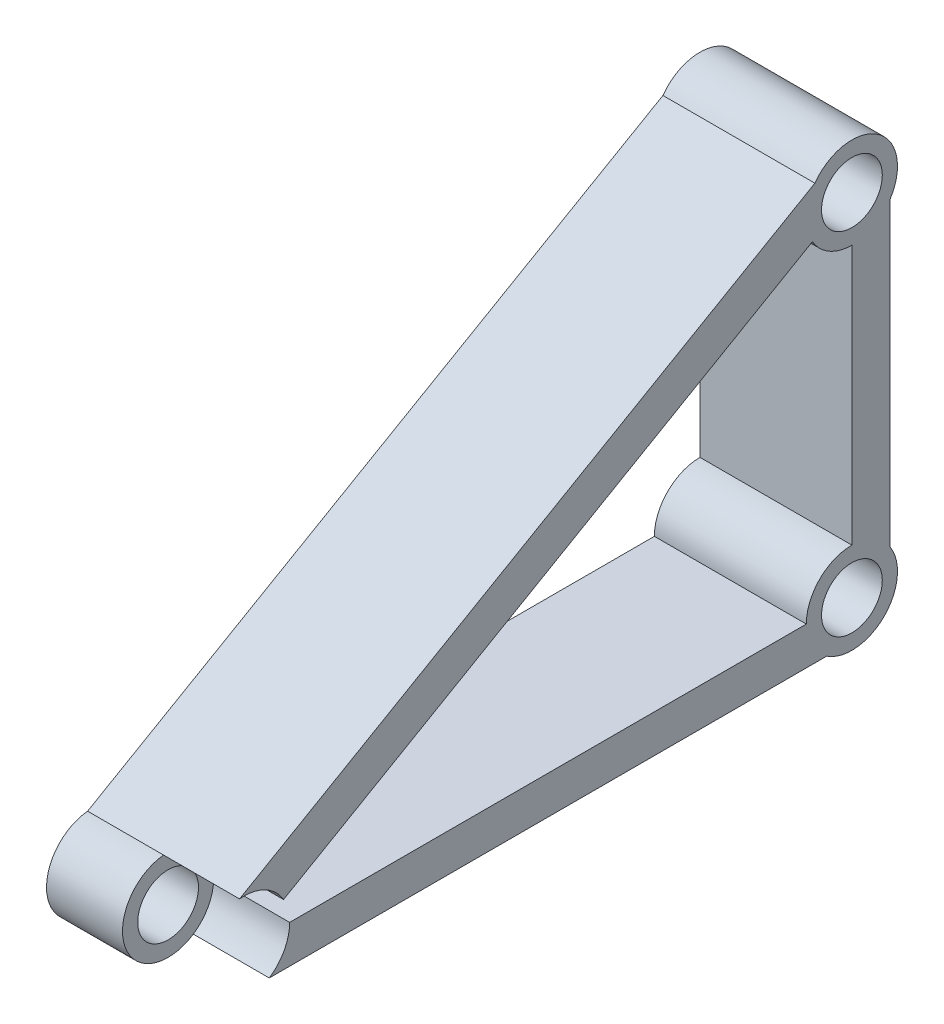
SolidWorks part; units mm, degrees
material "Thornel VCB-20 Carbon Cloth"
ref_plane "Front Plane" through (0, 0, 0) normal (0, 0, 1) x (1, 0, 0)
ref_plane "Top Plane" through (0, 0, 0) normal (0, 1, 0) x (1, 0, 0)
ref_plane "Right Plane" through (0, 0, 0) normal (1, 0, 0) x (0, 0, -1)
sketch "Sketch2" plane through (0, 0, 0) normal (1, 0, 0) x (0, 0, -1)
  line L0 (1528.6955, 519.1525) -> (1528.6955, 177.2722)
  line L2 (1476.734, 549.1525) -> (780.657, 147.2722)
  line L3 (722.7516, 176.9771) -> (1479.9615, 614.1525)
  line L4 (761.8617, 67.2722) -> (1495.5292, 67.2722)
  line L5 (1578.6955, 545.9862) -> (1578.6955, 150.4385)
  line L6 (1468.6955, 117.2722) -> (788.6955, 117.2722)
  line L7 (780.657, 147.2722) -> (728.6955, 117.2722) construction
  line L8 (728.6955, 117.2722) -> (788.6955, 117.2722) construction
  line L9 (1528.6955, 177.2722) -> (1528.6955, 117.2722) construction
  line L10 (1528.6955, 117.2722) -> (1468.6955, 117.2722) construction
  line L11 (1476.734, 549.1525) -> (1528.6955, 579.1525) construction
  line L12 (1528.6955, 579.1525) -> (1528.6955, 519.1525) construction
  line L13 (1479.9615, 614.1525) -> (1502.7147, 564.1525) construction
  arc A0 (780.657, 147.2722) -> (788.6955, 117.2722) centre (728.6955, 117.2722) ccw
  arc A1 (1528.6955, 519.1525) -> (1476.734, 549.1525) centre (1528.6955, 579.1525) ccw
  arc A2 (1468.6955, 117.2722) -> (1528.6955, 177.2722) centre (1528.6955, 117.2722) ccw
  circle A3 centre (728.6955, 117.2722) radius 40
  circle A4 centre (1528.6955, 579.1525) radius 40
  circle A5 centre (1528.6955, 117.2722) radius 40
  arc A6 (788.6955, 117.2722) -> (780.657, 147.2722) centre (728.6955, 117.2722) ccw
  arc A7 (1468.6955, 117.2722) -> (1528.6955, 177.2722) centre (1528.6955, 117.2722) cw
  arc A8 (1476.734, 549.1525) -> (1528.6955, 519.1525) centre (1528.6955, 579.1525) ccw
  dimension "D3" = 120
  dimension "D7" = 80
  dimension "D2" = 800
  dimension "D1" = 90
  dimension "D5" = 30
  dimension "D6" = 50
  dimension "D8" = 50
  dimension "D4" = 50
extrude "Boss-Extrude1" add sketch "Sketch2" along normal blind 200 contours A2 L6 A0 L4 | A1 L3 A0 L2 | A2 L5 A1 L0 | A0 A6 A3 | A7 A2 A5 | A1 A8 A4 region at (0, 348.2123, -1554.2791) region at (0, 528.6606, -1499.544) region at (0, 168.6446, -1556.2657) region at (0, 372.1927, -1114.8504) region at (0, 91.9722, -1128.6955) region at (0, 132.3622, -785.0118)
sketch "Sketch4" plane through (0, 0, 0) normal (1, 0, 0) x (0, 0, -1)
  circle A0 centre (728.6955, 117.2722) radius 60
  dimension "D1" = 120
extrude "Cut-Extrude1" cut sketch "Sketch4" against normal blind 100 from surface starting at face at (200, 272.2313, -1259.617)
equation "\"controlAngle\"= 30deg"
equation "\"baseLength\"= 80cm"
equation "\"D2@Sketch2\"=\"baseLength\""
equation "\"D3@Sketch2\"=1.5*\"HoleMountDiameter@PrintingPress.Assembly\""
equation "\"D7@Sketch2\"=\"HoleMountDiameter@PrintingPress.Assembly\""
equation "\"D5@Sketch2\"=\"controlAngle\""
equation "\"D8@Sketch2\"=0.5*\"RivetLength@PrintingPress.Assembly\""
equation "\"D4@Sketch2\"=0.5*\"RivetLength@PrintingPress.Assembly\""
equation "\"D1@Boss-Extrude1\"=2*\"RivetLength@PrintingPress.Assembly\""
equation "\"D1@Sketch4\"=1.5*\"HoleMountDiameter@PrintingPress.Assembly\""
equation "\"D1@Cut-Extrude1\"=\"RivetLength@PrintingPress.Assembly\""
